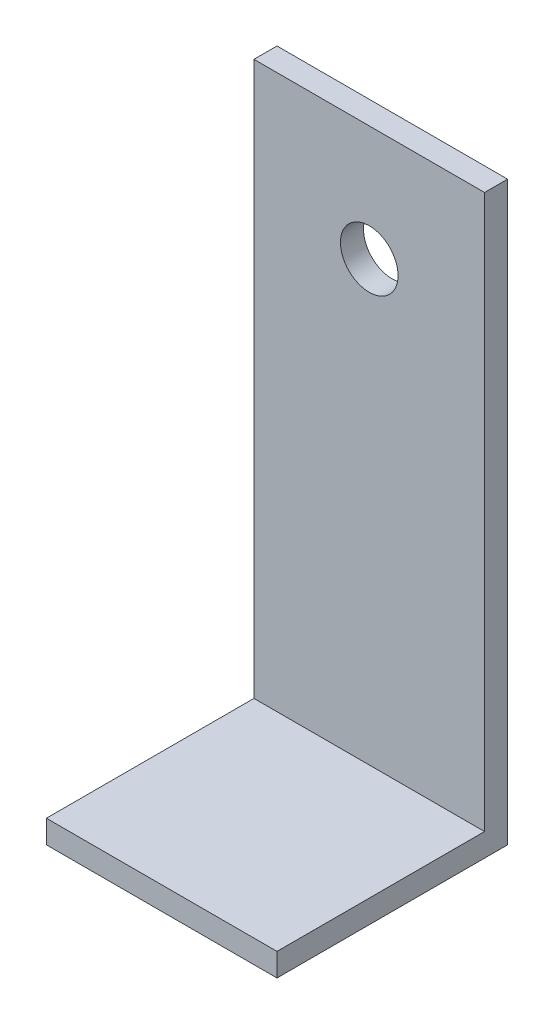
SolidWorks part; units mm, degrees
ref_plane "Front Plane" through (0, 0, 0) normal (0, 0, 1) x (1, 0, 0)
ref_plane "Top Plane" through (0, 0, 0) normal (0, 1, 0) x (1, 0, 0)
ref_plane "Right Plane" through (0, 0, 0) normal (1, 0, 0) x (0, 0, -1)
sketch "Sketch1" plane through (0, 0, 0) normal (1, 0, 0) x (0, 0, -1)
  line L0 (-25.4, 0) -> (0, 0)
  line L1 (0, 0) -> (0, 63.5)
  line L2 (-25.4, 0) -> (-25.4, 2.54)
  line L3 (-25.4, 2.54) -> (-2.54, 2.54)
  line L4 (-2.54, 2.54) -> (-2.54, 63.5)
  line L5 (-2.54, 63.5) -> (0, 63.5)
  dimension "D1" = 25.4
  dimension "D2" = 63.5
  dimension "D3" = 2.54
  dimension "D4" = 2.54
extrude "Boss-Extrude1" add sketch "Sketch1" along normal blind 12.7 and the other way blind 12.7
sketch "Sketch2" plane through (0, 0, 2.54) normal (0, 0, 1) x (1, 0, 0)
  line L0 (0, 63.5) -> (0, 0) construction
  line L1 (12.7, 63.5) -> (-12.7, 63.5) construction
  line L2 (-12.7, 0) -> (12.7, 0) construction
  circle A0 centre (0, 50.8) radius 3.175
  dimension "D1" = 6.35
  dimension "D2" = 50.8
extrude "Cut-Extrude1" cut sketch "Sketch2" against normal blind 12.7
